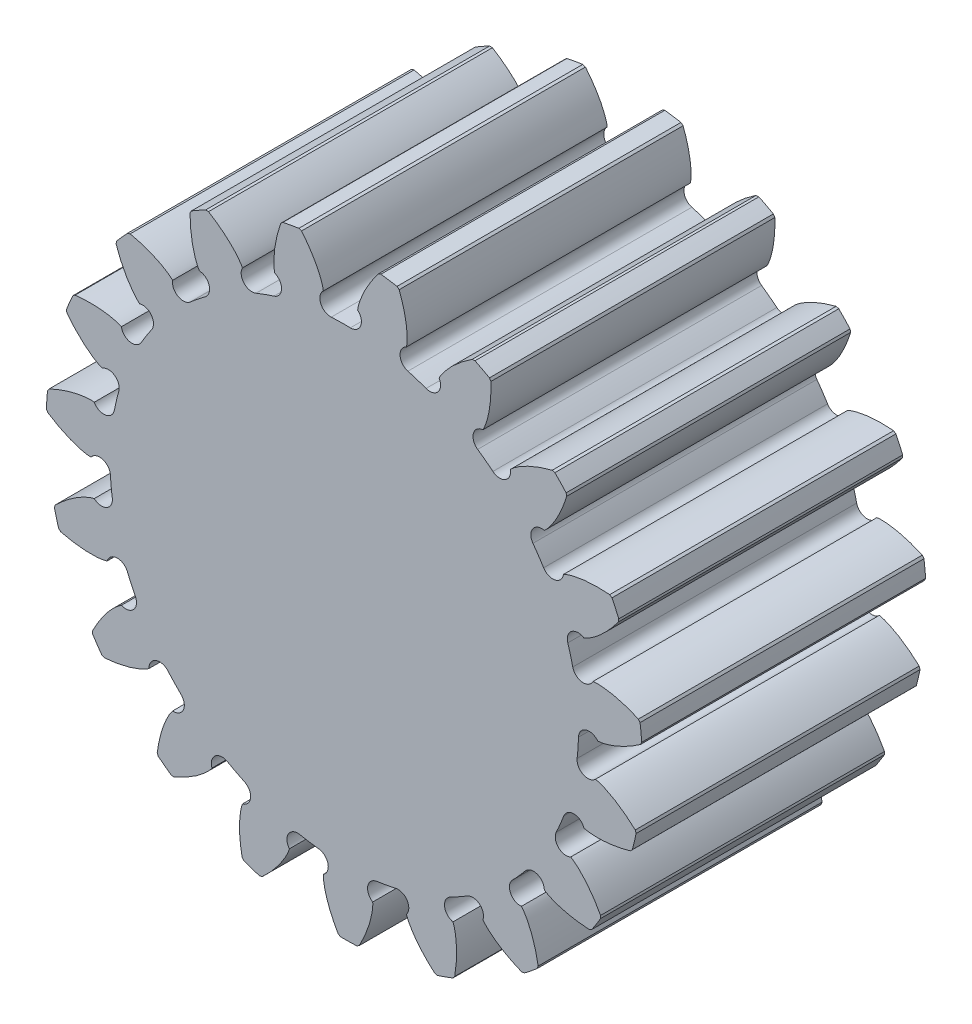
SolidWorks part; units mm, degrees
material "1.6587 (18CrNiMo7-6)"
ref_plane "Front Plane" through (0, 0, 0) normal (0, 0, 1) x (1, 0, 0)
ref_plane "Top Plane" through (0, 0, 0) normal (0, 1, 0) x (1, 0, 0)
ref_plane "Right Plane" through (0, 0, 0) normal (1, 0, 0) x (0, 0, -1)
sketch "Sketch1" plane through (0, 0, 0) normal (0, 0, 1) x (1, 0, 0)
  circle A2 centre (0, 0) radius 28.875
  dimension "D2" = 57.75
extrude "Boss-Extrude1" add sketch "Sketch1" along normal blind 35 contours A2
sketch "Sketch3" plane through (0, 0, 0) normal (0, 0, 1) x (1, 0, 0)
  line L0 (0, 0) -> (33.2463, 0.4956) construction
  line L1 (0, 0) -> (42.178, 4.1288) construction
  arc A0 (28.8645, -0.7794) -> (28.1654, 6.362) centre (0, 0) ccw
  circle A1 centre (0, 0) radius 33.25 construction
  arc A2 (36.6729, 2.3791) -> (36.4381, 4.7777) centre (0, 0) ccw
  arc A3 (31.2448, 0) -> (28.8645, -0.7794) centre (30.194, -0.8153) ccw
  arc A4 (30.6517, 6.059) -> (28.1654, 6.362) centre (29.4627, 6.655) cw
  spline S0 degree 4 poles (31.2448, 0) (31.2561, 0.0002) (31.2879, 0.0012) (31.3478, 0.0051) (31.4455, 0.0144) (31.5697, 0.0305) (31.7298, 0.0562) (31.9178, 0.0928) (32.1235, 0.1396) (32.3464, 0.1976) (32.5677, 0.2616) (32.7875, 0.3313) (33.0054, 0.4058) (33.2681, 0.5022) (33.5813, 0.6263) (33.9444, 0.7836) (34.3525, 0.9764) (34.764, 1.188) (35.1653, 1.4088) (35.5661, 1.646) (35.9506, 1.8856) (36.3448, 2.1487) (36.706, 2.3989) (37.1047, 2.6948) (37.4246, 2.9381) (37.8397, 3.2755) (38.0828, 3.4796) (38.3648, 3.7241) (38.4887, 3.8356) (38.5651, 3.9042) knots 0 0 0 0 0 0.005377 0.015084 0.028532 0.04661 0.064855 0.092111 0.119476 0.146842 0.174209 0.201575 0.228941 0.256307 0.307035 0.361767 0.4165 0.471232 0.525964 0.580697 0.635429 0.690161 0.744894 0.799626 0.854358 0.909091 0.954545 1 1 1 1 1 construction
  spline S1 degree 4 poles (31.2448, 0) (31.2561, 0.0002) (31.2879, 0.0012) (31.3478, 0.0051) (31.4455, 0.0144) (31.5697, 0.0305) (31.7298, 0.0562) (31.9178, 0.0928) (32.1235, 0.1396) (32.3464, 0.1976) (32.5677, 0.2616) (32.7875, 0.3313) (33.0054, 0.4058) (33.2681, 0.5022) (33.5813, 0.6263) (33.9444, 0.7836) (34.3525, 0.9764) (34.764, 1.188) (35.1653, 1.4088) (35.5661, 1.646) (35.9506, 1.8856) (36.285, 2.1088) (36.5051, 2.26) (36.6358, 2.3526) (36.6729, 2.3791) knots 0 0 0 0 0 0.005377 0.015084 0.028532 0.04661 0.064855 0.092111 0.119476 0.146842 0.174209 0.201575 0.228941 0.256307 0.307035 0.361767 0.4165 0.471232 0.525964 0.580697 0.635429 0.690161 0.711678 0.711678 0.711678 0.711678 0.711678
  spline S2 degree 4 poles (30.6517, 6.059) (30.6628, 6.061) (30.6942, 6.0662) (30.7537, 6.074) (30.8514, 6.0838) (30.9763, 6.092) (31.1384, 6.0978) (31.3299, 6.0984) (31.5408, 6.0924) (31.7707, 6.0788) (32.0002, 6.0589) (32.2293, 6.0332) (32.4576, 6.0023) (32.734, 5.9586) (33.0653, 5.8976) (33.452, 5.8138) (33.8897, 5.7038) (34.3345, 5.5759) (34.7709, 5.4372) (35.2101, 5.2822) (35.6338, 5.1217) (36.0051, 4.9676) (36.2504, 4.8619) (36.3966, 4.7965) (36.4381, 4.7777) knots 0 0 0 0 0 0.005377 0.015084 0.028532 0.04661 0.064855 0.092111 0.119476 0.146842 0.174209 0.201575 0.228941 0.256307 0.307035 0.361767 0.4165 0.471232 0.525964 0.580697 0.635429 0.690161 0.711678 0.711678 0.711678 0.711678 0.711678
  dimension "D1" = 66.5
  dimension "D2" = 73.5
  dimension "D3" = 57.75
  dimension "D4" = 2.66
  dimension "D5" = 4.737
extrude "Boss-Extrude2" add sketch "Sketch3" along normal blind 35
chamfer "Chamfer1" distance 0.2 2 edges at (36.4381, 4.7777, 17.5) (36.6729, 2.3791, 17.5)
pattern_circular "CirPattern1" count 19 over 360 about axis through (0, 0, 35) along (0, 0, -1) of "Boss-Extrude2", "Chamfer1"
